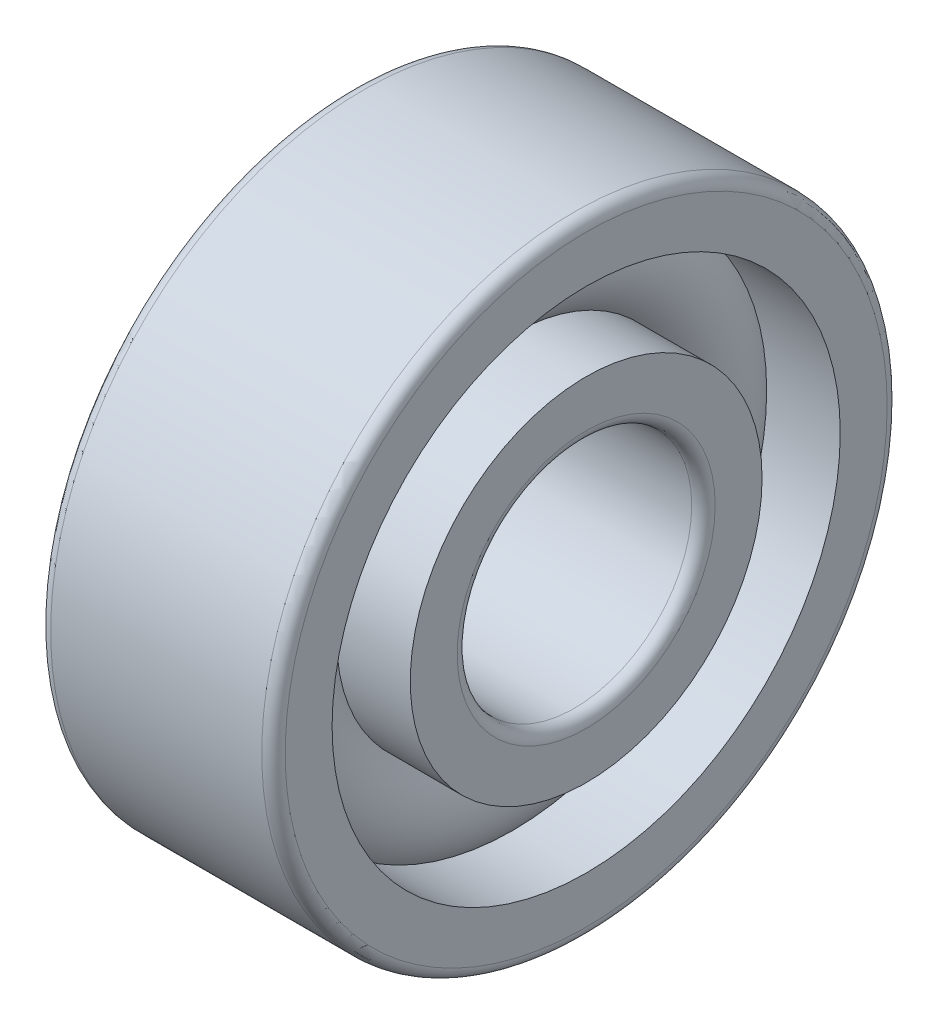
SolidWorks part; units mm, degrees
ref_plane "Plane1" through (0, 0, 0) normal (0, 0, 1) x (1, 0, 0)
ref_plane "Plane2" through (0, 0, 0) normal (0, 1, 0) x (1, 0, 0)
ref_plane "Plane3" through (0, 0, 0) normal (1, 0, 0) x (0, 0, -1)
sketch "Clipboard" plane through (0, 0, 0) normal (0, 0, 1) x (1, 0, 0)
  line L0 (-10, 0) -> (10, 0) construction
  line L1 (0, 0) -> (22.3471, -0.7804)
  line L2 (0, 0) -> (2.7483, 0.096)
  line L3 (0, 0) -> (22.3471, -0.7804)
  line L4 (0, 0) -> (-22.3573, -0.3902)
  dimension "BallCLRad" = 2.75
sketch "CagSpiSke" plane through (0, 0, 0) normal (0, 0, 1) x (1, 0, 0)
  line L0 (0.075, 2.625) -> (0.075, 2.875)
  line L1 (0.075, 2.875) -> (-0.075, 2.875)
  line L2 (-0.075, 2.875) -> (-0.075, 2.625)
  line L3 (-0.075, 2.625) -> (0.075, 2.625)
  line L4 (-20.6375, 0) -> (20.6375, 0) construction
  line L5 (0, 0) -> (0, 23.7692) construction
  dimension "OD" = 5.75
  dimension "ID" = 5.25
revolve "CageSpine" add sketch "CagSpiSke" angle 0.001 about L4 reverse direction yes
ref_axis "Axis1" through (-50, 0, 0) along (1, 0, 0)
sketch "CagBalSke" plane through (0, 0, 0) normal (0, 0, 1) x (1, 0, 0)
  line L0 (-0.825, 2.75) -> (0.825, 2.75)
  line L1 (-1.905, 2.75) -> (1.905, 2.75) construction
  line L2 (-10, 0) -> (10, 0) construction
  line L3 (0, 0) -> (0, 24) construction
  arc A0 (0.825, 2.75) -> (-0.825, 2.75) centre (0, 2.75) cw
  dimension "BallCLRad" = 2.75
revolve "CageBall" [suppressed] add sketch "CagBalSke" angle 360 about L1 reverse direction yes
pattern_circular "CageBalls" [suppressed] count 2 every 180 about axis through (-50, 0, 0) along (1, 0, 0)
sketch "CagTrmODSke" plane through (0, 0, 0) normal (0, 0, 1) x (1, 0, 0)
  line L0 (0.826, 2.875) -> (0.826, 3.576)
  line L1 (0.826, 3.576) -> (-0.826, 3.576)
  line L2 (-0.826, 3.576) -> (-0.826, 2.875)
  line L3 (-0.826, 2.875) -> (0.826, 2.875)
  line L4 (-20.6375, 0) -> (20.6375, 0) construction
  line L5 (0, 0) -> (0, 25) construction
  dimension "Width" = 1.652
  dimension "ID" = 5.75
  dimension "OD" = 7.152
revolve "CageTrimOD" [suppressed] cut sketch "CagTrmODSke" angle 360 about L4 reverse direction yes
sketch "CagTrmIDSke" plane through (0, 0, 0) normal (0, 0, 1) x (1, 0, 0)
  line L0 (0.826, 1.926) -> (0.826, 2.625)
  line L1 (0.826, 2.625) -> (-0.826, 2.625)
  line L2 (-0.826, 2.625) -> (-0.826, 1.926)
  line L3 (-0.826, 1.926) -> (0.826, 1.926)
  line L4 (-20.6375, 0) -> (20.6375, 0) construction
  line L5 (0, 0) -> (0, 25) construction
  dimension "Width" = 1.652
  dimension "ID" = 3.852
  dimension "OD" = 5.25
revolve "CageTrimID" [suppressed] cut sketch "CagTrmIDSke" angle 360 about L4 reverse direction yes
sketch "BalSimSke" plane through (0, 0, 0) normal (0, 0, 1) x (1, 0, 0)
  line L0 (-10, 0) -> (10, 0) construction
  line L1 (-10, 2.75) -> (10, 2.75) construction
  line L2 (0, 0) -> (0, 23) construction
  circle A0 centre (0, 2.75) radius 0.75
  dimension "BallCLRad" = 2.75
  dimension "Ball_diameter" = 1.5
revolve "BallsSimplified" add sketch "BalSimSke" angle 360 about L0
sketch "BalDetSke" plane through (0, 0, 0) normal (0, 0, 1) x (1, 0, 0)
  line L0 (-0.75, 2.75) -> (0.75, 2.75)
  line L1 (-1.905, 2.75) -> (1.905, 2.75) construction
  line L2 (0, 0) -> (0, 25) construction
  arc A0 (0.75, 2.75) -> (-0.75, 2.75) centre (0, 2.75) cw
  dimension "BallCLRad" = 2.75
  dimension "Ball_diameter" = 1.5
revolve "BallDetailed" [suppressed] add sketch "BalDetSke" angle 360 about L1 reverse direction yes
sketch "InnRacSke" plane through (0, 0, 0) normal (0, 0, 1) x (1, 0, 0)
  line L0 (-0.525, 2.25) -> (-1.5, 2.25)
  line L1 (-1.5, 2.25) -> (-1.5, 1.65)
  line L2 (-1.35, 1.5) -> (1.35, 1.5)
  line L3 (1.5, 1.65) -> (1.5, 2.25)
  line L4 (1.5, 2.25) -> (0.525, 2.25)
  line L5 (-20.6375, 0) -> (20.6375, 0) construction
  line L6 (0, 0) -> (0, 30) construction
  arc A0 (-1.5, 1.65) -> (-1.35, 1.5) centre (-1.35, 1.65) ccw
  arc A1 (1.35, 1.5) -> (1.5, 1.65) centre (1.35, 1.65) ccw
  arc A2 (0.525, 2.25) -> (-0.525, 2.25) centre (0, 2.75) cw
  dimension "BallCLRad" = 2.75
  dimension "Fillet_radius" = 0.15
  dimension "Ball_diameter" = 1.45
  dimension "ID" = 3
  dimension "OD" = 4.5
  dimension "Width" = 3
revolve "InnerRace" add sketch "InnRacSke" angle 360 about L5 reverse direction yes
sketch "OutRacSke" plane through (0, 0, 0) normal (0, 0, 1) x (1, 0, 0)
  line L0 (-0.525, 3.25) -> (-1.5, 3.25)
  line L1 (-1.5, 3.25) -> (-1.5, 3.85)
  line L2 (-1.35, 4) -> (1.35, 4)
  line L3 (1.5, 3.85) -> (1.5, 3.25)
  line L4 (1.5, 3.25) -> (0.525, 3.25)
  line L5 (-20.6375, 0) -> (20.6375, 0) construction
  line L6 (0, 0) -> (0, 30) construction
  arc A0 (-1.5, 3.85) -> (-1.35, 4) centre (-1.35, 3.85) cw
  arc A1 (1.35, 4) -> (1.5, 3.85) centre (1.35, 3.85) cw
  arc A2 (0.525, 3.25) -> (-0.525, 3.25) centre (0, 2.75) ccw
  dimension "BallCLRad" = 2.75
  dimension "Fillet_radius" = 0.15
  dimension "Ball_diameter" = 1.45
  dimension "Width" = 3
revolve "OuterRace" add sketch "OutRacSke" angle 360 about L5 reverse direction yes
pattern_circular "BallsDetailed" [suppressed] count 2 every 180 about axis through (-50, 0, 0) along (1, 0, 0)
equation "\"BallCLRad@Clipboard\" = ( \"OD@OutRacSke\" + \"ID@InnRacSke\" ) / 4"
equation "\"BallCLRad@BalSimSke\" = \"BallCLRad@Clipboard\""
equation "\"BallCLRad@BalDetSke\" = \"BallCLRad@Clipboard\""
equation "\"BallCLRad@InnRacSke\" = \"BallCLRad@Clipboard\""
equation "\"BallCLRad@OutRacSke\" = \"BallCLRad@Clipboard\""
equation "\"Ball_diameter@InnRacSke\" = \"Ball_diameter@BalDetSke\" - 0.05"
equation "\"Ball_diameter@OutRacSke\" = \"Ball_diameter@BalDetSke\" - 0.05"
equation "\"Ball_diameter@BalSimSke\" = \"Ball_diameter@BalDetSke\""
equation "\"Width@OutRacSke\" = \"Width@InnRacSke\""
equation "\"Fillet_radius@OutRacSke\" = \"Fillet_radius@InnRacSke\""
equation "\"Max_count@Clipboard\" = int( 3.14159265 / atn(( \"Ball_diameter@BalDetSke\" / 2) / sqr( \"BallCLRad@Clipboard\"  *  \"BallCLRad@Clipboard\" - ( \"Ball_diameter@BalDetSke\" / 2) *  ( \"Ball_diameter@BalDetSke\" / 2))))"
equation "\"Max_count@Clipboard\" = ((sgn( \"Max_count@Clipboard\" - \"Count@Clipboard\" )-1)*( \"Max_count@Clipboard\" - \"Count@Clipboard\" ))/-2+ \"Count@Clipboard\""
equation "\"Count@BallsDetailed\" = int( \"Show_count@Clipboard\" ) "
equation "\"Count@BallsDetailed\" = ((sgn( \"Count@BallsDetailed\" - \"Max_count@Clipboard\" )-1)*( \"Count@BallsDetailed\" - \"Max_count@Clipboard\" ))/-2+ \"Max_count@Clipboard\""
equation "\"Count@BallsDetailed\" = ((sgn( \"Count@BallsDetailed\" - \"Min_count@Clipboard\" )+1)*( \"Count@BallsDetailed\" - \"Min_count@Clipboard\"))/2 +\"Min_count@Clipboard\""
equation "\"Angle@BallsDetailed\" = 360.0 / \"Max_count@Clipboard\""
equation "\"BallCLRad@CagBalSke\" = \"BallCLRad@Clipboard\""
equation "\"Count@CageBalls\" = \"Count@BallsDetailed\""
equation "\"Angle@CageBalls\" = \"Angle@BallsDetailed\""
equation "\"Angle@CageSpine\" =  \"Angle@CageBalls\" * ( \"Count@CageBalls\" -1 + int( \"Count@CageBalls\" / \"Max_count@Clipboard\" ) )  + 0.001 -  int( \"Count@CageBalls\" / \"Max_count@Clipboard\" ) * 0.001"
equation "\"Angle@CageSpine\" =  \"Angle@CageSpine\" * int( \"Min_count@Clipboard\" / 2) + int(1 / \"Min_count@Clipboard\")  * 0.001"
equation "\"CageWallOD@CagBalSke\" =  \"Ball_diameter@BalDetSke\" * 1.1"
equation "\"Thickness@CagSpiSke\" =  \"Ball_diameter@BalDetSke\" * 0.1"
equation "\"OD@CagTrmODSke\" = \"BallCLRad@Clipboard\" * 2 + \"CageWallOD@CagBalSke\" + 0.002"
equation "\"ID@CagTrmODSke\" = \"BallCLRad@Clipboard\" * 2 + \"Ball_diameter@BalDetSke\" / 6"
equation "\"OD@CagTrmIDSke\" = \"BallCLRad@Clipboard\" * 2 - \"Ball_diameter@BalDetSke\" / 6"
equation "\"ID@CagTrmIDSke\" = \"BallCLRad@Clipboard\" * 2 - \"CageWallOD@CagBalSke\" + 0.002"
equation "\"OD@CagSpiSke\" = \"ID@CagTrmODSke\""
equation "\"ID@CagSpiSke\" = \"OD@CagTrmIDSke\""
equation "\"Width@CagTrmODSke\" = \"CageWallOD@CagBalSke\" + 0.002"
equation "\"Width@CagTrmIDSke\" = \"CageWallOD@CagBalSke\" + 0.002"
